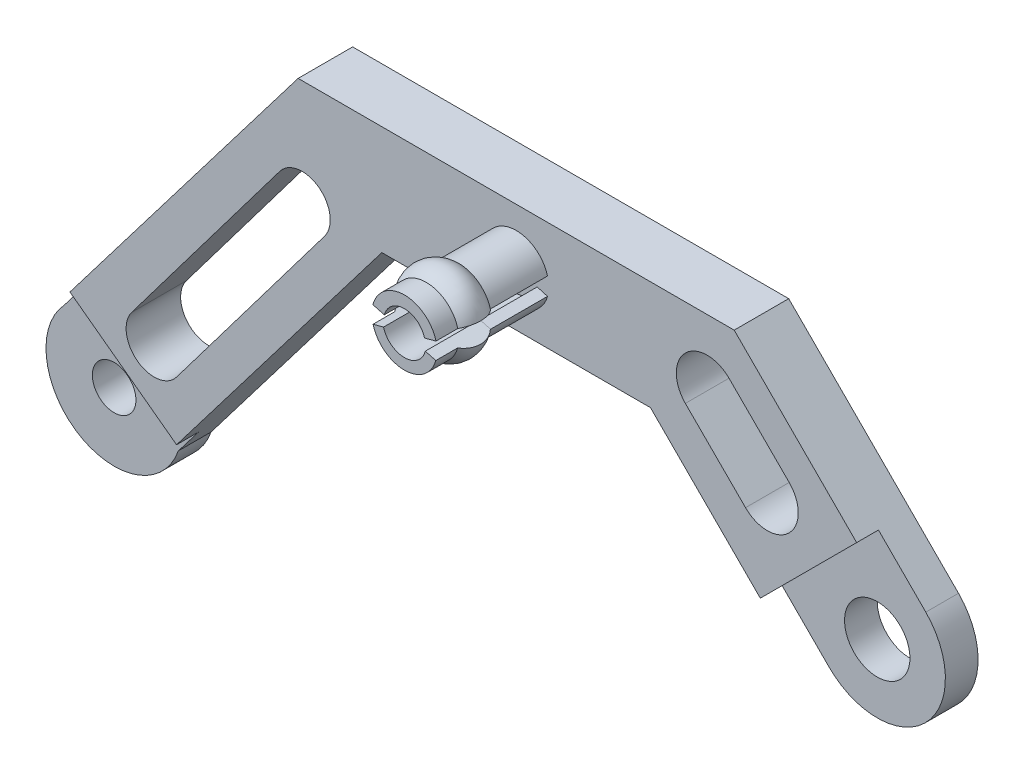
SolidWorks part; units mm, degrees
ref_plane "Płaszczyzna przednia" through (0, 0, 0) normal (0, 0, 1) x (1, 0, 0)
ref_plane "Płaszczyzna górna" through (0, 0, 0) normal (0, 1, 0) x (1, 0, 0)
ref_plane "Płaszczyzna prawa" through (0, 0, 0) normal (1, 0, 0) x (0, 0, -1)
sketch "Szkic1" plane through (0, 0, 0) normal (0, 0, 1) x (1, 0, 0)
  line L0 (-20, 0) -> (20, 0)
  line L1 (-12.3211, -10) -> (12.3211, -10)
  line L2 (-20, 0) -> (-43.4519, -30.7392)
  line L3 (-12.3211, -10) -> (-32.9894, -37.0907)
  line L4 (12.3211, -10) -> (26.6118, -24.3281)
  line L5 (20, 0) -> (35.5748, -15.6156)
  arc A0 (-43.4519, -30.7392) -> (-32.9894, -37.0907) centre (-38.8794, -35) ccw
  arc A1 (26.6118, -24.3281) -> (35.5748, -15.6156) centre (31.1206, -20) ccw
  circle A2 centre (-38.8794, -35) radius 2
  circle A3 centre (31.1206, -20) radius 3
  point P2 (0, 0)
  point P3 (0, -10)
  dimension "D6" = 6.25
  dimension "D1" = 40
  dimension "D2" = 10
  dimension "D3" = 10
  dimension "D4" = 70
  dimension "D5" = 35
extrude "Dodanie-wyciągnięcie1" add sketch "Szkic1" along normal blind 5
sketch "Szkic3" plane through (0, 0, 0) normal (0, 0, -1) x (-1, 0, 0)
  line L0 (19.6296, -9.7758) -> (33.2072, -27.7594) construction
  line L1 (21.683, -8.2254) -> (35.2607, -26.209)
  line L2 (17.5761, -11.3262) -> (31.1537, -29.3098)
  arc A0 (21.683, -8.2254) -> (17.5761, -11.3262) centre (19.6296, -9.7758) ccw
  arc A1 (31.1537, -29.3098) -> (35.2607, -26.209) centre (33.2072, -27.7594) ccw
  point P2 (26.4184, -18.7676)
extrude "Wytnij-wyciągnięcie2" cut sketch "Szkic3" against normal blind 10
sketch "Szkic4" plane through (0, 0, 0) normal (0, 0, -1) x (-1, 0, 0)
  line L0 (-17.5195, -6.0599) -> (-23.0418, -11.5822) construction
  line L1 (-15.5177, -8.0618) -> (-21.04, -13.5841)
  line L2 (-19.5214, -4.0581) -> (-25.0437, -9.5804)
  arc A0 (-15.5177, -8.0618) -> (-19.5214, -4.0581) centre (-17.5195, -6.0599) ccw
  arc A1 (-25.0437, -9.5804) -> (-21.04, -13.5841) centre (-23.0418, -11.5822) ccw
  point P2 (-20.2807, -8.8211)
extrude "Wytnij-wyciągnięcie4" cut sketch "Szkic4" against normal blind 10
sketch "Szkic5" plane through (0, 0, 5) normal (0, 0, 1) x (1, 0, 0)
  line L2 (-1.9225, -4.5282) -> (-2.8786, -4.2597)
  line L3 (-1.9255, -5.6091) -> (-2.8786, -5.8768)
  line L4 (1.9255, -4.5274) -> (2.8786, -4.2597)
  line L5 (1.9255, -5.6091) -> (2.8786, -5.8768)
  arc A2 (-2.8786, -4.2597) -> (2.8786, -4.2597) centre (0, -5.0682) cw
  arc A3 (-2.8786, -5.8768) -> (2.8786, -5.8768) centre (0, -5.0682) ccw
  arc A4 (-1.9255, -5.6091) -> (1.9255, -5.6091) centre (0, -5.0682) ccw
  arc A5 (-1.9225, -4.5282) -> (1.9255, -4.5274) centre (0.0016, -5.0764) cw
  point P1 (0.0016, -5.0764)
  point P6 (0, -5.0682)
  point P8 (0, -5.0682)
extrude "Dodanie-wyciągnięcie2" add sketch "Szkic5" along normal blind 5.25
sketch "Szkic6" plane through (0, 0, 0) normal (1, 0, 0) x (0, 0, -1)
  line L0 (-10.25, -2.0782) -> (-10.25, -3.169)
  line L2 (-10.25, -2.0782) -> (-10.25, -4.2597) construction
  line L3 (-10.25, -3.169) -> (-13.25, -3.169)
  line L5 (-13.25, -3.169) -> (-15.25, -3.169)
  line L6 (-15.25, -3.169) -> (-15.25, -2.0782)
  line L7 (-15.25, -2.0782) -> (-13.25, -2.0782)
  line L8 (-10.25, -5.0764) -> (-16.033, -5.0764) construction
  arc A0 (-13.25, -2.0782) -> (-10.25, -2.0782) centre (-11.75, -3.5782) cw
sketch3d "Szkic 3D1"
  line L0 (0.0016, -5.0764, 10.25) -> (0.0016, -5.0764, -3.8761) construction
  line L1 (0.0016, -5.0764, 10.25) -> (0.0016, -5.0764, 5) construction
revolve "Obrót1" add sketch "Szkic6" angle 75 about L8 other way angle 75
sketch "Szkic7" plane through (0, 0, 0) normal (1, 0, 0) x (0, 0, -1)
  line L0 (-10.25, -8.0582) -> (-10.25, -7.0582)
  line L2 (-10.25, -5.8768) -> (-10.25, -8.0582) construction
  line L3 (-10.25, -7.0582) -> (-13.25, -7.0582)
  line L5 (-13.25, -7.0582) -> (-15.25, -7.0582)
  line L6 (-15.25, -7.0582) -> (-15.25, -8.0582)
  line L7 (-15.25, -8.0582) -> (-13.25, -8.0582)
  line L8 (-10.25, -5.0764) -> (-16.0253, -5.0764) construction
  arc A0 (-13.25, -8.0582) -> (-10.25, -8.0582) centre (-11.75, -6.5582) ccw
revolve "Obrót2" add sketch "Szkic7" angle 75 about L8 other way angle 75
sketch3d "Szkic 3D2" plane through (0, 0, 0) normal (0, 0, 1) x (1, 0, 0)
  dimension "D1" = 5
sketch "Szkic8" plane through (0, 0, 5) normal (0, 0, 1) x (1, 0, 0)
  line L0 (32.4189, -10.076) -> (21.2648, -21.2301)
  line L1 (21.2648, -21.2301) -> (33.2671, -33.2324)
  line L2 (33.2671, -33.2324) -> (44.4212, -22.0783)
  line L3 (44.4212, -22.0783) -> (32.4189, -10.076)
  line L4 (-43.1055, -25.8261) -> (-28.0781, -36.9575)
  line L5 (-28.0781, -36.9575) -> (-36.7261, -48.6324)
  line L6 (-36.7261, -48.6324) -> (-51.7536, -37.501)
  line L7 (-51.7536, -37.501) -> (-43.1055, -25.8261)
extrude "Wytnij-wyciągnięcie5" cut sketch "Szkic8" against normal blind 2
